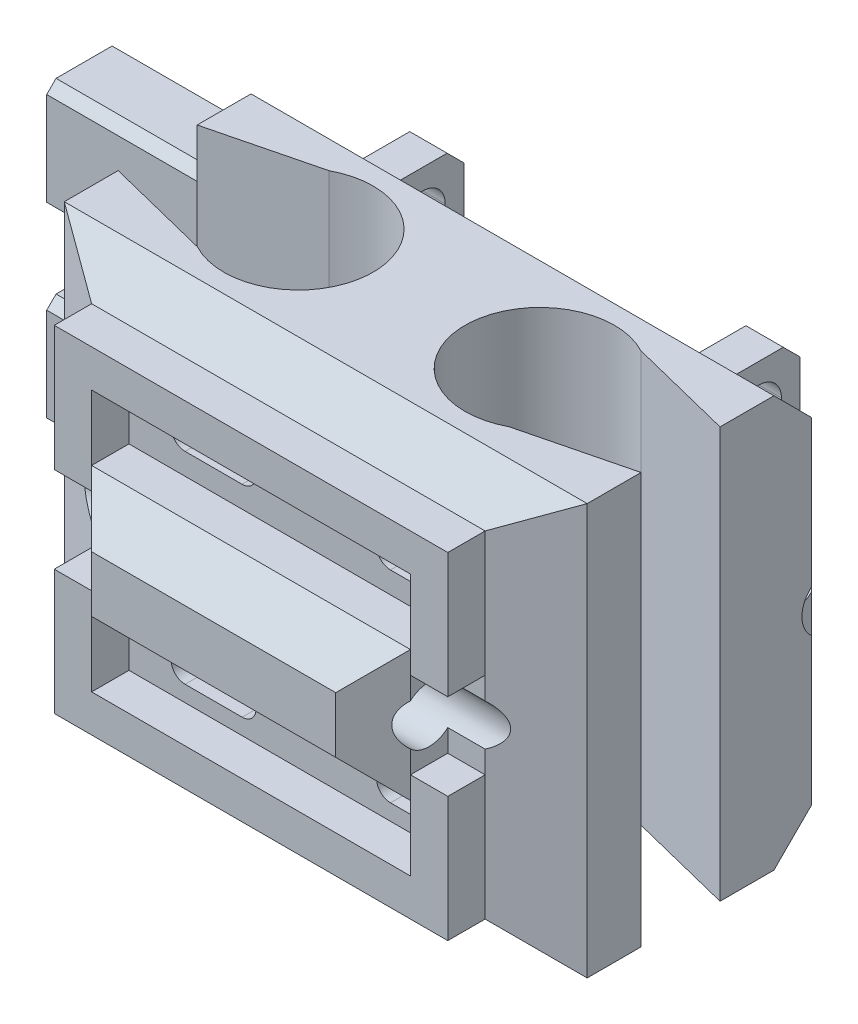
SolidWorks part; units mm, degrees
ref_plane "Front Plane" through (0, 0, 0) normal (0, 0, 1) x (1, 0, 0)
ref_plane "Top Plane" through (0, 0, 0) normal (0, 1, 0) x (1, 0, 0)
ref_plane "Right Plane" through (0, 0, 0) normal (1, 0, 0) x (0, 0, -1)
sketch "Base" plane through (0, 0, 0) normal (0, 0, 1) x (1, 0, 0)
  line L1 (0, 0) -> (14, 0)
  line L2 (0, 0) -> (0, 11)
  line L3 (0, 11) -> (14, 11)
  line L4 (14, 0) -> (14, 11)
  dimension "D1" = 14
  dimension "D2" = 11
extrude "Phalange shape" add sketch "Base" along normal blind 7
chamfer "Chamfer4" distance 1 angle 45 2 edges at (7, 11, 7) (7, 0, 7)
chamfer "Chamfer5" distance 1 angle 60 2 edges at (0, 5.5, 7) (14, 5.5, 7)
chamfer "Chamfer6" distance 1 angle 45 2 edges at (7, 11, 0) (7, 0, 0)
sketch "Sketch8" plane through (0, 0, 7) normal (0, 0, 1) x (1, 0, 0)
  line L0 (12.2679, 5.5) -> (1.7321, 5.5) construction
  line L1 (12.2679, 1) -> (12.2679, 10) construction
  line L2 (1.7321, 10) -> (1.7321, 1) construction
  line L3 (7, 1) -> (7, 10) construction
  line L4 (1.7321, 1) -> (12.2679, 1) construction
  line L5 (12.2679, 10) -> (1.7321, 10) construction
  line L6 (2.7321, 3.75) -> (2.7321, 7.25)
  line L7 (11.2679, 7.25) -> (2.7321, 7.25)
  line L8 (11.2679, 7.25) -> (11.2679, 3.75)
  line L9 (11.2679, 3.75) -> (2.7321, 3.75)
  point P17 (2.7321, 5.5)
  point P18 (11.2679, 5.5)
  dimension "D1" = 1.75
  dimension "D2" = 1
  dimension "D3" = 1
extrude "Ligament inside" add sketch "Sketch8" along normal blind 2
sketch "Sketch9" plane through (11.2679, 0, 0) normal (1, 0, 0) x (0, 0, -1)
  line L0 (-9, 5.5) -> (-7, 5.5) construction
  line L1 (-9, 3.75) -> (-9, 7.25) construction
  line L2 (-7, 3.75) -> (-7, 7.25) construction
  circle A0 centre (-7.5, 5.5) radius 0.75
  dimension "D1" = 1.5
  dimension "D2" = 1.5
extrude "Ligament inside hole" cut sketch "Sketch9" against normal blind 34.5 and the other way blind 4.2544
chamfer "Chamfer9" distance 1 angle 45 4 edges at (2.7321, 5.5, 9) (7, 7.25, 9) (11.2679, 5.5, 9) (7, 3.75, 9)
sketch "Sketch10" plane through (0, 0, 0) normal (0, 0, -1) x (-1, 0, 0)
  line L0 (-7, 1) -> (-7, 10) construction
  line L1 (-14, 1) -> (0, 1) construction
  line L2 (0, 10) -> (-14, 10) construction
  line L3 (0, 5.5) -> (-14, 5.5) construction
  line L4 (0, 10) -> (0, 1) construction
  line L5 (-14, 1) -> (-14, 10) construction
  line L6 (-1, 7.25) -> (-13, 7.25)
  line L8 (-1, 7.25) -> (-1, 3.75)
  line L9 (-1, 3.75) -> (-13, 3.75)
  line L10 (-13, 7.25) -> (-13, 3.75)
  point P17 (-13, 5.5)
  point P18 (-1, 5.5)
  dimension "D1" = 1.75
  dimension "D2" = 1
  dimension "D3" = 1
extrude "Ligament outside" add sketch "Sketch10" along normal blind 2
sketch "Sketch11" plane through (1, 0, 0) normal (-1, 0, 0) x (0, 0, 1)
  line L0 (-2, 5.5) -> (0, 5.5) construction
  line L1 (-2, 3.75) -> (-2, 7.25) construction
  line L2 (0, 3.75) -> (0, 7.25) construction
  circle A0 centre (-0.5, 5.5) radius 0.75
  dimension "D1" = 1.5
  dimension "D2" = 1.5
extrude "Ligament outside hole" cut sketch "Sketch11" against normal blind 36.5 and the other way blind 2.5
chamfer "Chamfer11" distance 1 angle 45 4 edges at (7, 7.25, -2) (1, 5.5, -2) (7, 3.75, -2) (13, 5.5, -2)
sketch "Tendon extrude" plane through (0, 0, 0) normal (0, -1, 0) x (1, 0, 0)
  line L0 (7, 6) -> (7, -3.9632) construction
  line L1 (14, 6) -> (0, 6) construction
  line L2 (0, 3.5) -> (21.7648, 3.5) construction
  line L3 (0, 6) -> (0, 1) construction
  line L4 (3.77, 4) -> (-2.23, 4)
  line L5 (3.77, 1.5) -> (-2.23, 3)
  line L6 (3.77, 4) -> (3.77, 3)
  line L7 (3.77, 3) -> (-2.23, 3)
  line L8 (-2.23, 4) -> (-2.23, 3)
  line L9 (3.77, 5.5) -> (-2.23, 4)
  line L10 (10.23, 4) -> (10.23, 3)
  line L11 (10.23, 1.5) -> (16.23, 3)
  line L12 (10.23, 3) -> (16.23, 3)
  line L13 (10.23, 3) -> (10.23, 4)
  line L14 (10.23, 4) -> (16.23, 4)
  line L15 (16.23, 3) -> (16.23, 4)
  line L16 (16.23, 4) -> (10.23, 5.5)
  circle A0 centre (3.77, 3.5) radius 2
  circle A1 centre (10.23, 3.5) radius 2
  point P16 (-2.23, 3.5)
  dimension "D1" = 4
  dimension "D2" = 3.77
  dimension "D3" = 1
  dimension "D4" = 6
  dimension "D5" = 6
extrude "Tendons fixation" cut sketch "Tendon extrude" against normal blind 11
sketch "Sketch12" plane through (0, 0, 0) normal (0, 0, -1) x (-1, 0, 0)
  line L0 (-7, 10) -> (-7, 1) construction
  line L1 (0, 10) -> (-14, 10) construction
  line L2 (-14, 1) -> (0, 1) construction
  line L3 (-2, 4.75) -> (-2, 6.25) construction
  line L4 (-2, 10) -> (-3, 10)
  line L5 (-2, 10) -> (-2, 6.25)
  line L6 (-2, 6.25) -> (-3, 6.25)
  line L7 (-3, 10) -> (-3, 6.25)
  line L8 (-2, 4.75) -> (-3, 4.75)
  line L9 (-2, 4.75) -> (-2, 1)
  line L10 (-2, 1) -> (-3, 1)
  line L11 (-3, 4.75) -> (-3, 1)
  line L12 (-2, 6.25) -> (-12, 6.25) construction
  line L13 (-12, 4.75) -> (-2, 4.75) construction
  line L14 (-12, 1) -> (-11, 1)
  line L15 (-12, 4.75) -> (-12, 1)
  line L16 (-11, 4.75) -> (-11, 1)
  line L17 (-12, 4.75) -> (-11, 4.75)
  line L18 (-12, 10) -> (-11, 10)
  line L19 (-11, 10) -> (-11, 6.25)
  line L20 (-12, 6.25) -> (-11, 6.25)
  line L21 (-12, 10) -> (-12, 6.25)
  dimension "D2" = 1
extrude "Boss-Extrude7" add sketch "Sketch12" along normal blind 2
sketch "Sketch13" plane through (2, 0, 0) normal (-1, 0, 0) x (0, 0, 1)
  line L0 (-0.6, 8.85) -> (-0.6, 7.85) construction
  line L1 (0, 8.85) -> (0, 7.85)
  line L2 (-1.2, 8.85) -> (-1.2, 7.85)
  line L4 (0, 3.75) -> (-1, 3.75) construction
  line L5 (0, 7.25) -> (0, 10) construction
  line L6 (-1, 7.25) -> (0, 7.25) construction
  line L7 (-0.6, 3.15) -> (-0.6, 2.15) construction
  line L8 (0, 3.15) -> (0, 2.15)
  line L9 (-1.2, 3.15) -> (-1.2, 2.15)
  arc A0 (0, 8.85) -> (-1.2, 8.85) centre (-0.6, 8.85) ccw
  arc A1 (-1.2, 7.85) -> (0, 7.85) centre (-0.6, 7.85) ccw
  arc A2 (0, 3.15) -> (-1.2, 3.15) centre (-0.6, 3.15) ccw
  arc A3 (-1.2, 2.15) -> (0, 2.15) centre (-0.6, 2.15) ccw
  point P2 (-0.6, 8.35)
  point P7 (-0.6, 2.65)
  dimension "D1" = 0
  dimension "D2" = 0.6
  dimension "D3" = 0.6
  dimension "D4" = 0.6
  dimension "D5" = 1
extrude "Touch sensor wire gauge" cut sketch "Sketch13" against normal blind 12
chamfer "Chamfer12" distance 0.3 angle 45 8 edges at (11, 8.125, -2) (12, 8.125, -2) (12, 2.875, -2) (11, 2.875, -2) (2, 2.875, -2) (3, 2.875, -2) (3, 8.125, -2) (2, 8.125, -2)
chamfer "Chamfer13" distance 0.75 angle 45 4 edges at (11.5, 10, -2) (11.5, 1, -2) (2.5, 1, -2) (2.5, 10, -2)
sketch "Sketch15" plane through (0, 0, 0) normal (-1, 0, 0) x (0, 0, 1)
  line L0 (0.25, 5.5) -> (2.4425, 5.5) construction
  line L1 (2.4425, 11) -> (2.4425, 0) construction
  line L2 (0, 9.5) -> (2, 9.5)
  line L3 (0, 4.5) -> (2, 4.5)
  line L4 (0, 4.5) -> (0, 1.5)
  line L5 (0, 1.5) -> (2, 1.5)
  line L6 (2, 4.5) -> (2, 1.5)
  line L7 (2, 6.5) -> (2, 9.5)
  line L8 (0, 6.5) -> (0, 9.5)
  line L9 (0, 6.5) -> (2, 6.5)
  line L12 (0, 4.941) -> (0, 1) construction
  arc A0 (0, 4.941) -> (0, 6.059) centre (-0.5, 5.5) ccw construction
  dimension "D1" = 2
  dimension "D3" = 3
  dimension "D4" = 1
extrude "Boss-Extrude8" add sketch "Sketch15" along normal blind 4.47
chamfer "Chamfer14" distance 0.25 angle 45 8 edges at (-2.235, 6.5, 2) (-2.235, 9.5, 2) (-2.235, 9.5, 0) (-2.235, 6.5, 0) (-2.235, 4.5, 0) (-2.235, 4.5, 2) (-2.235, 1.5, 2) (-2.235, 1.5, 0)
chamfer "Chamfer15" distance 0.5 angle 45 4 edges at (0, 9.5, 1) (0, 1.5, 1) (0, 4.5, 1) (0, 6.5, 1)
sketch "Sketch16" plane through (0, 0, 7) normal (0, 0, 1) x (1, 0, 0)
  line L0 (12.2679, 1) -> (12.2679, 4.941) construction
  line L1 (1.7321, 1) -> (12.2679, 1)
  line L2 (1.7321, 1) -> (1.7321, 2)
  line L3 (1.7321, 2) -> (12.2679, 2)
  line L4 (12.2679, 1) -> (12.2679, 2)
  line L5 (11.2679, 3.75) -> (11.2679, 4.941) construction
  line L6 (11.2679, 4.3455) -> (12.2679, 4.3455)
  line L7 (11.2679, 4.3455) -> (11.2679, 2)
  line L8 (11.2679, 2) -> (12.2679, 2)
  line L9 (12.2679, 4.3455) -> (12.2679, 2)
  line L10 (2.7321, 4.941) -> (2.7321, 3.75) construction
  line L11 (2.7321, 4.3455) -> (1.7321, 4.3455)
  line L12 (2.7321, 4.3455) -> (2.7321, 2)
  line L13 (2.7321, 2) -> (1.7321, 2)
  line L14 (1.7321, 4.3455) -> (1.7321, 2)
  line L15 (12.2679, 6.059) -> (12.2679, 10) construction
  line L16 (1.7321, 10) -> (12.2679, 10)
  line L17 (1.7321, 10) -> (1.7321, 9)
  line L18 (1.7321, 9) -> (12.2679, 9)
  line L19 (12.2679, 10) -> (12.2679, 9)
  line L20 (2.7321, 7.25) -> (2.7321, 6.059) construction
  line L21 (2.7321, 6.6545) -> (1.7321, 6.6545)
  line L22 (2.7321, 6.6545) -> (2.7321, 9)
  line L23 (2.7321, 9) -> (1.7321, 9)
  line L24 (1.7321, 6.6545) -> (1.7321, 9)
  line L25 (11.2679, 6.059) -> (11.2679, 7.25) construction
  line L26 (11.2679, 6.6545) -> (12.2679, 6.6545)
  line L27 (11.2679, 6.6545) -> (11.2679, 9)
  line L28 (11.2679, 9) -> (12.2679, 9)
  line L29 (12.2679, 6.6545) -> (12.2679, 9)
  line M2 (1.7321, 4.941) -> (1.7321, 1)
  line M3 (1.7321, 1) -> (12.2679, 1)
  line M4 (12.2679, 1) -> (12.2679, 4.941)
  line M6 (11.2679, 4.941) -> (11.2679, 3.75)
  line M8 (2.7321, 3.75) -> (2.7321, 4.941)
extrude "Boss-Extrude9" add sketch "Sketch16" along normal blind 1 contours L12 L11 L3 M8 M2 | L3 M2 M3 M4 | L7 L3 L6 M6 M4 | L26 L29 L18 L27 | L19 L16 L17 L18 | L24 L21 L22 L18
sketch "Sketch17" plane through (0, 0, 7) normal (0, 0, 1) x (1, 0, 0)
  line L0 (4.2345, 8.2) -> (5.7625, 8.2) construction
  line L1 (4.2345, 8.5716) -> (5.7625, 8.5716)
  line L2 (4.2345, 7.8284) -> (5.7625, 7.8284)
  line L3 (9.7336, 8.2) -> (11.2616, 8.2) construction
  line L4 (9.7336, 8.5716) -> (11.2616, 8.5716)
  line L5 (9.7336, 7.8284) -> (11.2616, 7.8284)
  line L6 (4.2345, 2.8) -> (5.7625, 2.8) construction
  line L7 (4.2345, 3.1716) -> (5.7625, 3.1716)
  line L8 (4.2345, 2.4284) -> (5.7625, 2.4284)
  line L9 (9.7336, 2.8) -> (11.2616, 2.8) construction
  line L10 (9.7336, 3.1716) -> (11.2616, 3.1716)
  line L11 (9.7336, 2.4284) -> (11.2616, 2.4284)
  line L12 (2.7321, 9) -> (11.2679, 9) construction
  line L13 (2.7321, 2) -> (11.2679, 2) construction
  arc A0 (4.2345, 8.5716) -> (4.2345, 7.8284) centre (4.2345, 8.2) ccw
  arc A1 (5.7625, 7.8284) -> (5.7625, 8.5716) centre (5.7625, 8.2) ccw
  arc A2 (9.7336, 8.5716) -> (9.7336, 7.8284) centre (9.7336, 8.2) ccw
  arc A3 (11.2616, 7.8284) -> (11.2616, 8.5716) centre (11.2616, 8.2) ccw
  arc A4 (4.2345, 3.1716) -> (4.2345, 2.4284) centre (4.2345, 2.8) ccw
  arc A5 (5.7625, 2.4284) -> (5.7625, 3.1716) centre (5.7625, 2.8) ccw
  arc A6 (9.7336, 3.1716) -> (9.7336, 2.4284) centre (9.7336, 2.8) ccw
  arc A7 (11.2616, 2.4284) -> (11.2616, 3.1716) centre (11.2616, 2.8) ccw
  point P2 (4.9985, 8.2)
  point P7 (10.4976, 8.2)
  point P16 (4.9985, 2.8)
  point P21 (10.4976, 2.8)
  dimension "D1" = 0.8
  dimension "D2" = 0.8
extrude "Cut-Extrude1" cut sketch "Sketch17" against normal blind 1
